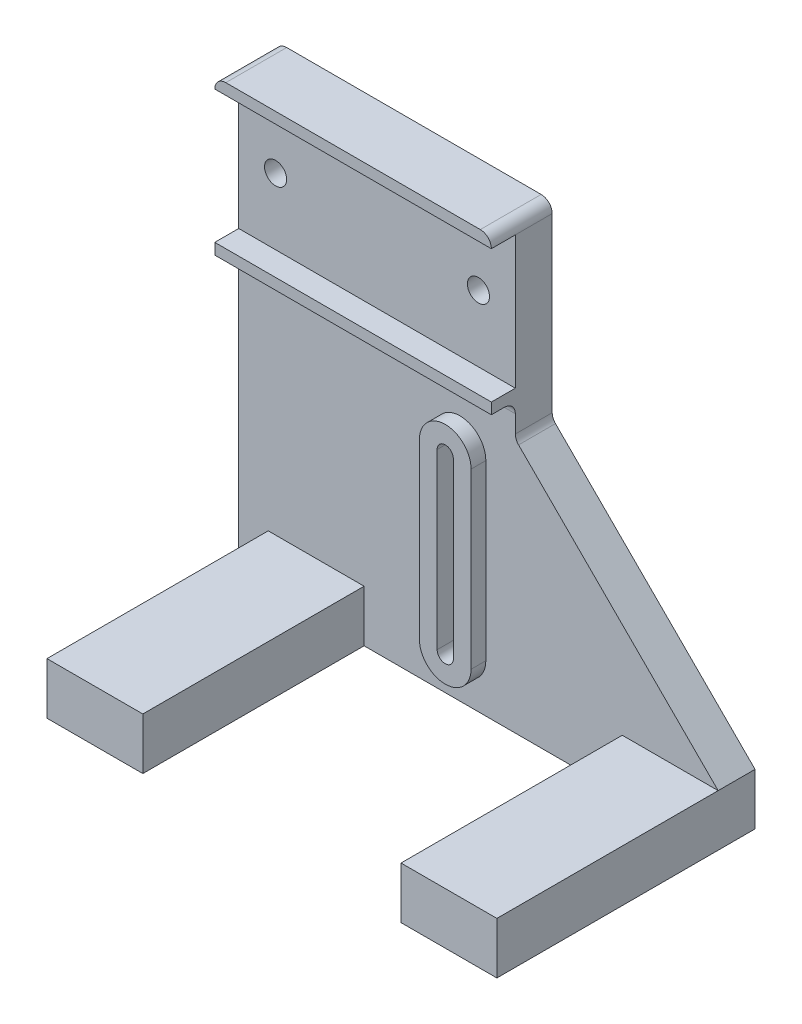
SolidWorks part; units mm, degrees
material "PET"
ref_plane "Front Plane" through (0, 0, 0) normal (0, 0, 1) x (1, 0, 0)
ref_plane "Top Plane" through (0, 0, 0) normal (0, 1, 0) x (1, 0, 0)
ref_plane "Right Plane" through (0, 0, 0) normal (1, 0, 0) x (0, 0, -1)
sketch "Sketch2" plane through (0, 0, 0) normal (0, 0, 1) x (1, 0, 0)
  line L0 (0, 0) -> (130, 0)
  line L1 (130, 0) -> (130, 14)
  line L2 (130, 14) -> (75, 69)
  line L3 (75, 69) -> (75, 120)
  line L4 (75, 120) -> (0, 120)
  line L5 (0, 120) -> (0, 0)
  dimension "D1" = 120
  dimension "D2" = 75
  dimension "D3" = 14
  dimension "D4" = 55
  dimension "D5" = 130
extrude "Boss-Extrude1" add sketch "Sketch2" against normal blind 10
sketch "Sketch3" plane through (0, 0, 0) normal (0, 0, 1) x (1, 0, 0)
  line L0 (75, 69) -> (75, 120) construction
  line L1 (0, 120) -> (75, 120)
  line L2 (0, 120) -> (0, 117)
  line L3 (0, 117) -> (75, 117)
  line L4 (75, 120) -> (75, 117)
  line L5 (0, 120) -> (75, 117) construction
  line L6 (0, 117) -> (75, 120) construction
  line L7 (0, 120) -> (0, 0) construction
  line L8 (0, 81) -> (75, 81)
  line L9 (0, 81) -> (0, 78)
  line L10 (0, 78) -> (75, 78)
  line L11 (75, 81) -> (75, 78)
  line L12 (0, 81) -> (75, 78) construction
  line L13 (0, 78) -> (75, 81) construction
  point P4 (37.5, 118.5)
  point P12 (37.5, 79.5)
  dimension "D1" = 3
  dimension "D2" = 36
extrude "Boss-Extrude2" add sketch "Sketch3" along normal blind 6.5
sketch "Sketch4" plane through (0, 0, 0) normal (0, 0, 1) x (1, 0, 0)
  line L0 (0, 99) -> (75, 99) construction
  line L1 (0, 117) -> (0, 81) construction
  line L2 (75, 81) -> (75, 117) construction
  circle A0 centre (10, 99) radius 3
  circle A1 centre (65, 99) radius 3
  dimension "D1" = 10
  dimension "D3" = 6
  dimension "D2" = 10
extrude "Cut-Extrude2" cut sketch "Sketch4" against normal up to surface (10 mm away) up to face at (68.3333, 53.8333, -10)
sketch "Sketch5" plane through (0, 0, 0) normal (0, 0, 1) x (1, 0, 0)
  line L0 (0, 0) -> (130, 0) construction
  line L1 (130, 14) -> (104, 14)
  line L2 (130, 14) -> (130, 0)
  line L3 (130, 0) -> (104, 0)
  line L4 (104, 14) -> (104, 0)
  line L5 (130, 14) -> (104, 0) construction
  line L6 (130, 0) -> (104, 14) construction
  line L7 (69, 0) -> (69, 120) construction
  line L8 (75, 120) -> (0, 120) construction
  line L9 (8, 0) -> (34, 0)
  line L10 (34, 14) -> (34, 0)
  line L11 (8, 14) -> (34, 14)
  line L12 (8, 14) -> (8, 0)
  line L13 (0, 78) -> (0, 0) construction
  point P4 (117, 7)
  dimension "D1" = 26
  dimension "D2" = 8
extrude "Boss-Extrude3" add sketch "Sketch5" along normal blind 60
sketch "Sketch6" plane through (0, 0, 0) normal (0, 0, 1) x (1, 0, 0)
  line L0 (0, 16) -> (6, 16) construction
  line L1 (0, 78) -> (0, 0) construction
  line L2 (0, 13) -> (6, 7)
  line L3 (6, 7) -> (6, 25)
  line L4 (6, 25) -> (0, 19)
  line L5 (8, 0) -> (34, 0) construction
  line L6 (0, 19) -> (0, 13)
  line L7 (0, 36) -> (-23.6105, 36) construction
  line L8 (0, 56) -> (6, 56) construction
  line L9 (6, 47) -> (0, 53)
  line L10 (6, 65) -> (6, 47)
  line L11 (0, 59) -> (6, 65)
  line L12 (0, 53) -> (0, 59)
  dimension "D1" = 6
  dimension "D2" = 6
  dimension "D3" = 16
  dimension "D4" = 6
  dimension "D5" = 40
sketch "Sketch7" plane through (0, 0, 0) normal (0, 0, 1) x (1, 0, 0)
  line L0 (60, 0) -> (60, 120) construction
  line L1 (34, 0) -> (104, 0) construction
  line L2 (75, 120) -> (0, 120) construction
  line L3 (60, 13) -> (60, 60) construction
  line L4 (53, 13) -> (53, 60)
  line L5 (67, 13) -> (67, 60)
  arc A0 (53, 13) -> (67, 13) centre (60, 13) ccw
  arc A1 (67, 60) -> (53, 60) centre (60, 60) ccw
  point P4 (60, 36.5)
  point P14 (60, 6)
  point P15 (60, 67)
  dimension "D1" = 26
  dimension "D2" = 7
  dimension "D3" = 6
extrude "Boss-Extrude5" add sketch "Sketch7" along normal blind 4
sketch "Sketch8" plane through (0, 0, 4) normal (0, 0, 1) x (1, 0, 0)
  line L4 (62.2, 13) -> (62.2, 60)
  line L5 (57.8, 60) -> (57.8, 13)
  line L6 (62.2, 13) -> (62.2, 60)
  line L7 (57.8, 60) -> (57.8, 13)
  arc A4 (57.8, 13) -> (62.2, 13) centre (60, 13) ccw
  arc A5 (62.2, 60) -> (57.8, 60) centre (60, 60) ccw
  arc A6 (57.8, 13) -> (62.2, 13) centre (60, 13) ccw
  arc A7 (62.2, 60) -> (57.8, 60) centre (60, 60) ccw
  dimension "D1" = 4.8
extrude "Cut-Extrude3" cut sketch "Sketch8" against normal through all
fillet "Fillet2" radius 3 4 edges at (75, 120, -1.75) (0, 120, -1.75) (37.5, 78, 0) (75, 69, -5)
extrude "Cut-Extrude4" [suppressed] cut sketch "Sketch6" against normal through all
fillet "Fillet3" [suppressed] radius 1.25
